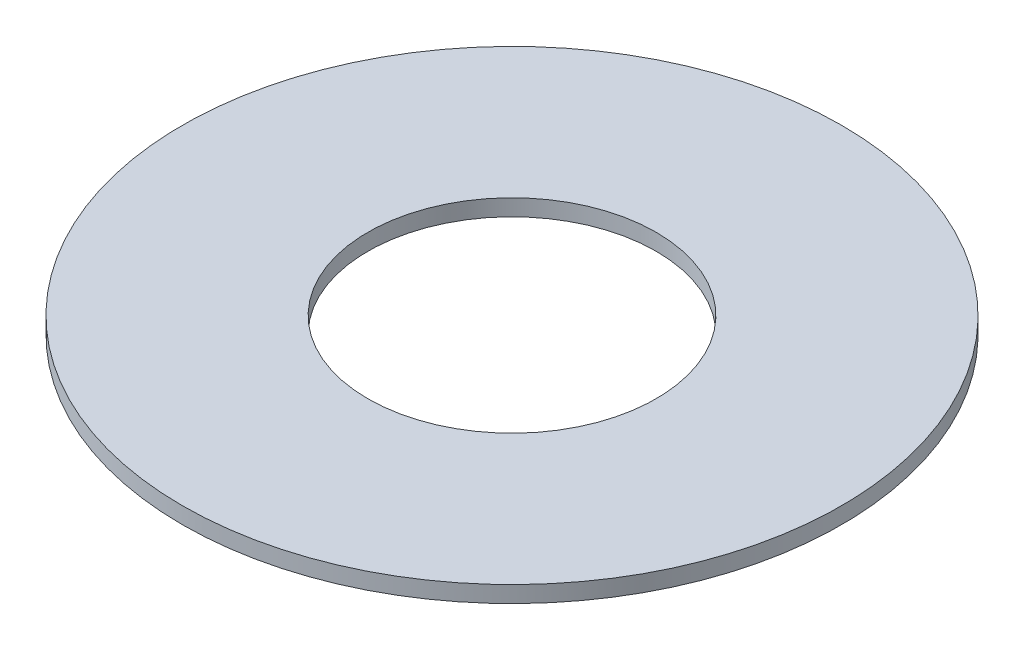
SolidWorks part; units mm, degrees
ref_plane "Front Plane" through (0, 0, 0) normal (0, 0, 1) x (1, 0, 0)
ref_plane "Top Plane" through (0, 0, 0) normal (0, 1, 0) x (1, 0, 0)
ref_plane "Right Plane" through (0, 0, 0) normal (1, 0, 0) x (0, 0, -1)
sketch "Sketch1" plane through (0, 0, 0) normal (0, 1, 0) x (1, 0, 0)
  circle A0 centre (0, 0) radius 80
  dimension "FLANGE_OD" = 160
extrude "Boss-Extrude1" add sketch "Sketch1" along normal blind 4
sketch "Sketch2" plane through (0, 0, 0) normal (0, 1, 0) x (1, 0, 0)
  circle A0 centre (0, 0) radius 35
  dimension "BORE_D" = 70
extrude "Cut-Extrude1" cut sketch "Sketch2" along normal through all
sketch "Sketch3" plane through (0, 4, 0) normal (0, 1, 0) x (1, 0, 0)
  circle A0 centre (0, 0) radius 28.8152 construction
  circle A1 centre (-28.8152, 0) radius 3.1886
  dimension "BOLT_D" = 6.3772
  dimension "BOLT_PCD" = 57.6305
extrude "Cut-Extrude2" cut sketch "Sketch3" against normal blind 3.2273 rebuild error yes
pattern_circular "CirPattern1" count 8 over 360 rebuild error yes
